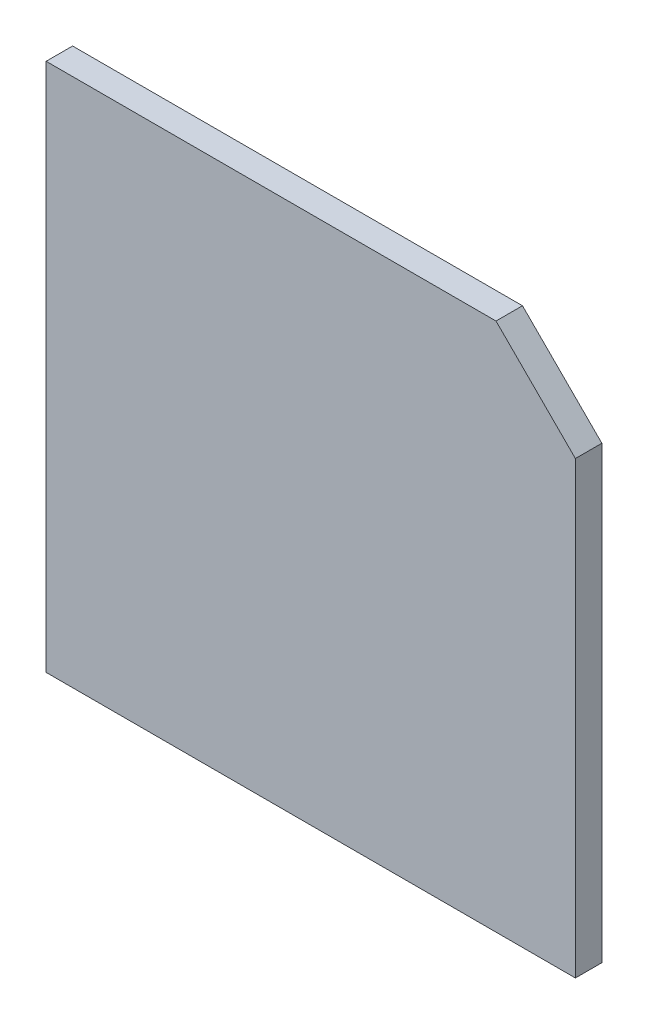
SolidWorks part; units mm, degrees
ref_plane "Front Plane" through (0, 0, 0) normal (0, 0, 1) x (1, 0, 0)
ref_plane "Top Plane" through (0, 0, 0) normal (0, 1, 0) x (1, 0, 0)
ref_plane "Right Plane" through (0, 0, 0) normal (1, 0, 0) x (0, 0, -1)
sketch "Sketch3" plane through (0, 0, 0) normal (0, 0, 1) x (1, 0, 0)
  line L0 (250, 250) -> (250, -250)
  line L1 (-250, -250) -> (250, -250)
  line L2 (-250, -250) -> (-250, 250)
  line L3 (-250, 250) -> (250, 250)
  dimension "plate_length" = 500
  dimension "plate_width" = 500
  dimension "D2" = 250
  dimension "D3" = 250
extrude "Boss-Extrude2" add sketch "Sketch3" along normal blind 25
sketch "Sketch4" plane through (0, 0, 25) normal (0, 0, 1) x (1, 0, 0)
  line L0 (175, 250) -> (250, 175)
  line L1 (250, 250) -> (-250, 250) construction
  line L2 (250, -250) -> (250, 250) construction
  line L3 (250, 175) -> (250, 250)
  line L4 (250, 250) -> (175, 250)
  dimension "D1" = 75
  dimension "D2" = 75
extrude "Cut-Extrude1" cut sketch "Sketch4" against normal blind 25.4
ref_axis "Axis1" through (0, 275, 0) along (0, -1, 0)
ref_axis "Axis2" through (275, 0, 0) along (-1, 0, 0)
equation "\"D3@Sketch3\"=\"plate_width@Sketch3\"/2"
equation "\"D2@Sketch3\"=\"plate_length@Sketch3\"/2"
